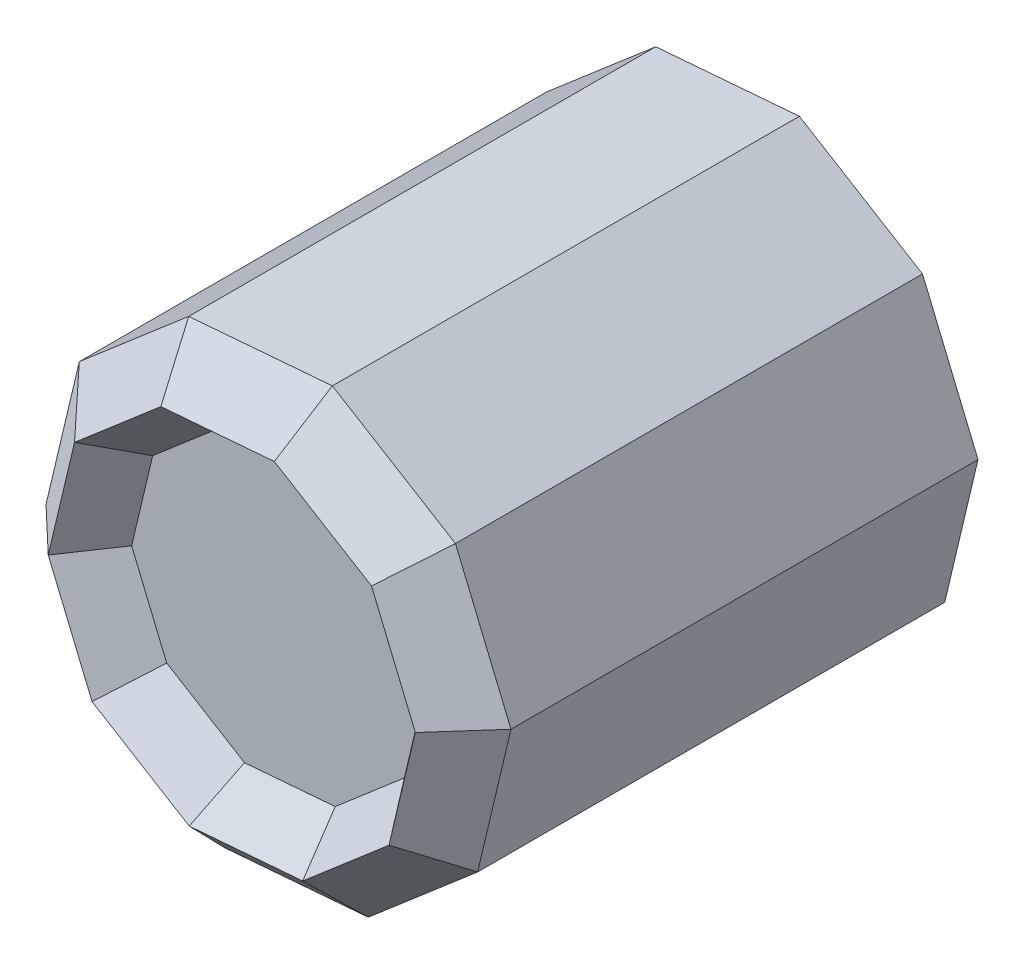
SolidWorks part; units mm, degrees
ref_plane "前视基准面" through (0, 0, 0) normal (0, 0, 1) x (1, 0, 0)
ref_plane "上视基准面" through (0, 0, 0) normal (0, 1, 0) x (1, 0, 0)
ref_plane "右视基准面" through (0, 0, 0) normal (1, 0, 0) x (0, 0, -1)
other "Configuration Table"
sketch "草图1" plane through (0, 0, 0) normal (0, 0, 1) x (1, 0, 0)
  line L1 (1.1536, 4.8594) -> (-1.923, 4.6094)
  line L2 (-1.923, 4.6094) -> (-4.2651, 2.5987)
  line L3 (-4.2651, 2.5987) -> (-4.978, -0.4045)
  line L4 (-4.978, -0.4045) -> (-3.7895, -3.2533)
  line L5 (-3.7895, -3.2533) -> (-1.1536, -4.8594)
  line L6 (-1.1536, -4.8594) -> (1.923, -4.6094)
  line L7 (1.923, -4.6094) -> (4.2651, -2.5987)
  line L8 (4.2651, -2.5987) -> (4.978, 0.4045)
  line L9 (4.978, 0.4045) -> (3.7895, 3.2533)
  line L10 (3.7895, 3.2533) -> (1.1536, 4.8594)
  circle A0 centre (0, 0) radius 3.05
  circle A1 centre (0, 0) radius 4.75 construction
  dimension "D1" = 6.1
  dimension "D2" = 9.5
extrude "凸台-拉伸1" add sketch "草图1" along normal blind 11
sketch "草图2" plane through (0, 0, 11) normal (0, 0, 1) x (1, 0, 0)
  circle A0 centre (0, 0) radius 3.0982
extrude "凸台-拉伸2" add sketch "草图2" against normal blind 2
sketch "草图3" plane through (0, 0, 9) normal (0, 0, -1) x (-1, 0, 0)
  line L1 (1.45, 2.6833) -> (1.45, -2.6833)
  circle A1 centre (0, 0) radius 3.05 construction
  circle A2 centre (0, 0) radius 3.05 construction
  arc A3 (1.45, -2.6833) -> (1.45, 2.6833) centre (0, 0) ccw
  point P1 (-3.05, 0)
  dimension "D1" = 4.5
extrude "凸台-拉伸3" add sketch "草图3" along normal blind 7
chamfer "倒角1" distance 1 angle 45 10 edges at (4.3838, 1.8289, 11) (4.6216, -1.0971, 11) (3.0941, -3.6041, 11) (0.3847, -4.7344, 11) (-2.4716, -4.0563, 11) (-4.3838, -1.8289, 11) (-4.6216, 1.0971, 11) (-3.0941, 3.6041, 11) (-0.3847, 4.7344, 11) (2.4716, 4.0563, 11)
ref_plane "基准面1" through (0, 0, 10) normal (0, 0, 1) x (1, 0, 0)
sketch "草图4" plane through (0, 0, 10) normal (0, 0, 1) x (1, 0, 0)
  line L0 (1.1536, 4.8594) -> (-1.1536, -4.8594) construction
  line L1 (0.7286, 3.0691) -> (-1.2145, 2.9112)
  line L2 (-1.2145, 2.9112) -> (-2.6937, 1.6413)
  line L3 (-2.6937, 1.6413) -> (-3.144, -0.2555)
  line L4 (-3.144, -0.2555) -> (-2.3934, -2.0547)
  line L5 (-2.3934, -2.0547) -> (-0.7286, -3.0691)
  line L6 (-0.7286, -3.0691) -> (1.2145, -2.9112)
  line L7 (1.2145, -2.9112) -> (2.6937, -1.6413)
  line L8 (2.6937, -1.6413) -> (3.144, 0.2555)
  line L9 (3.144, 0.2555) -> (2.3934, 2.0547)
  line L10 (2.3934, 2.0547) -> (0.7286, 3.0691)
  circle A0 centre (0, 0) radius 3 construction
  dimension "D1" = 6
sketch "草图5" plane through (0, 0, 11) normal (0, 0, 1) x (1, 0, 0)
  line L1 (0.9107, 3.8364) -> (-1.5182, 3.639)
  line L2 (-1.5182, 3.639) -> (-3.3672, 2.0516)
  line L3 (-3.3672, 2.0516) -> (-3.93, -0.3194)
  line L4 (-3.93, -0.3194) -> (-2.9917, -2.5684)
  line L5 (-2.9917, -2.5684) -> (-0.9107, -3.8364)
  line L6 (-0.9107, -3.8364) -> (1.5182, -3.639)
  line L7 (1.5182, -3.639) -> (3.3672, -2.0516)
  line L8 (3.3672, -2.0516) -> (3.93, 0.3194)
  line L9 (3.93, 0.3194) -> (2.9917, 2.5684)
  line L10 (2.9917, 2.5684) -> (0.9107, 3.8364)
  circle A0 centre (0, 0) radius 3.75 construction
loft "切除-放样1" cut profiles "草图5", "草图4" connector at (-1.5182, 3.639, 11) connector at (-1.2145, 2.9112, 10)
